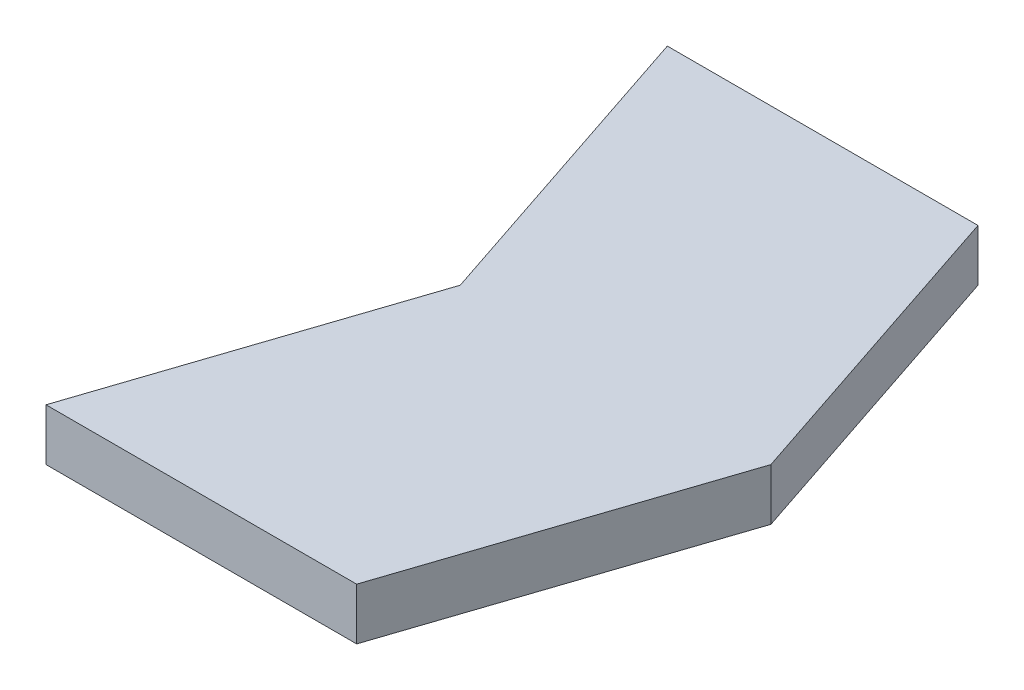
SolidWorks part; units mm, degrees
material "1060 Alloy"
ref_plane "Front Plane" through (0, 0, 0) normal (0, 0, 1) x (1, 0, 0)
ref_plane "Top Plane" through (0, 0, 0) normal (0, 1, 0) x (1, 0, 0)
ref_plane "Right Plane" through (0, 0, 0) normal (1, 0, 0) x (0, 0, -1)
sketch "Sketch1" plane through (0, 0, 0) normal (0, 1, 0) x (1, 0, 0)
  line L0 (0, 0) -> (19.05, 0)
  line L1 (19.05, 0) -> (25.4, 19.05)
  line L2 (25.4, 19.05) -> (19.05, 38.1)
  line L3 (19.05, 38.1) -> (0, 38.1)
  line L4 (0, 38.1) -> (6.35, 19.05)
  line L5 (6.35, 19.05) -> (0, 0)
  dimension "D1" = 19.05
  dimension "D2" = 38.1
  dimension "D3" = 6.35
  dimension "D5" = 19.05
extrude "Boss-Extrude1" add sketch "Sketch1" along normal blind 3.175
